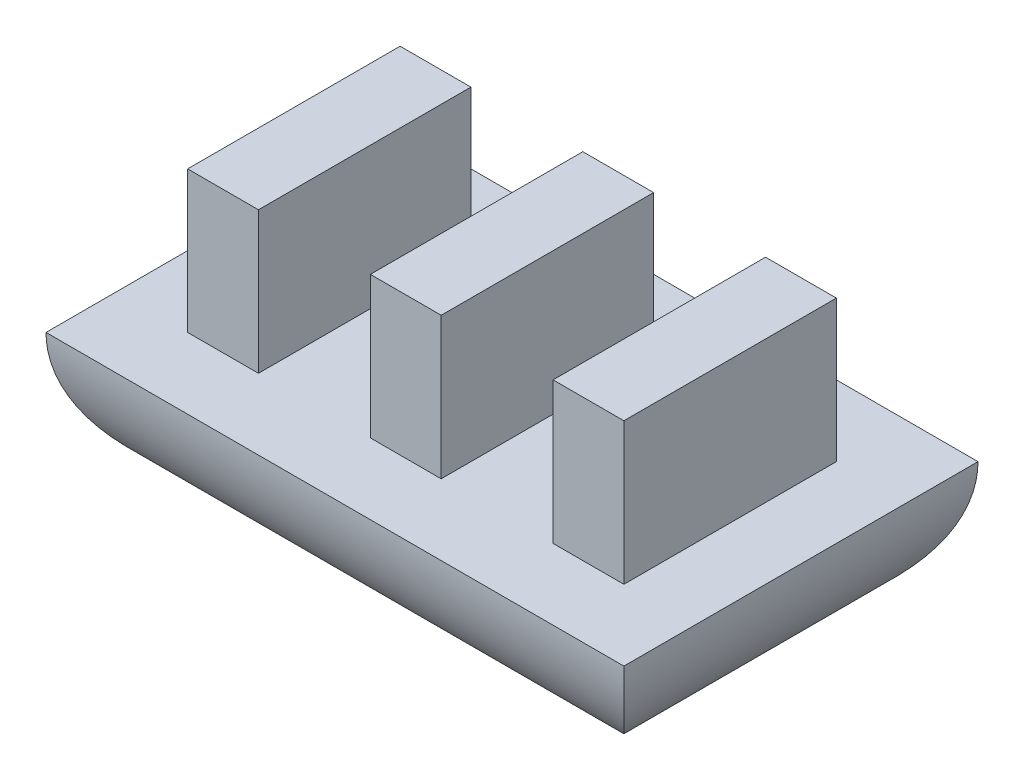
SolidWorks part; units mm, degrees
material "Silicon"
ref_plane "Front Plane" through (0, 0, 0) normal (0, 0, 1) x (1, 0, 0)
ref_plane "Top Plane" through (0, 0, 0) normal (0, 1, 0) x (1, 0, 0)
ref_plane "Right Plane" through (0, 0, 0) normal (1, 0, 0) x (0, 0, -1)
sketch "Sketch1" plane through (0, 0, 0) normal (0, 1, 0) x (1, 0, 0)
  line L0 (0, 3.9688) -> (12.954, 3.9688) construction
  line L1 (0, 0) -> (12.954, 0)
  line L2 (0, 0) -> (0, 7.9375)
  line L3 (0, 7.9375) -> (12.954, 7.9375)
  line L4 (12.954, 0) -> (12.954, 7.9375)
  line L6 (1.5875, 1.5875) -> (3.175, 1.5875)
  line L7 (1.5875, 1.5875) -> (1.5875, 6.35)
  line L8 (1.5875, 6.35) -> (3.175, 6.35)
  line L9 (3.175, 1.5875) -> (3.175, 6.35)
  line L10 (1.5875, 1.5875) -> (3.175, 6.35) construction
  line L11 (1.5875, 6.35) -> (3.175, 1.5875) construction
  line L12 (5.6833, 1.5875) -> (7.2707, 1.5875)
  line L13 (5.6833, 1.5875) -> (5.6833, 6.35)
  line L14 (5.6833, 6.35) -> (7.2707, 6.35)
  line L15 (7.2707, 1.5875) -> (7.2707, 6.35)
  line L16 (5.6833, 1.5875) -> (7.2707, 6.35) construction
  line L17 (5.6833, 6.35) -> (7.2707, 1.5875) construction
  line L18 (9.779, 1.5875) -> (11.3665, 1.5875)
  line L19 (9.779, 1.5875) -> (9.779, 6.35)
  line L20 (9.779, 6.35) -> (11.3665, 6.35)
  line L21 (11.3665, 1.5875) -> (11.3665, 6.35)
  line L22 (9.779, 1.5875) -> (11.3665, 6.35) construction
  line L23 (9.779, 6.35) -> (11.3665, 1.5875) construction
  point P7 (2.3813, 3.9688)
  point P12 (6.477, 3.9688)
  point P17 (10.5727, 3.9688)
  dimension "D1" = 1.5875
  dimension "D2" = 1.5875
  dimension "D3" = 12.954
  dimension "D4" = 1.5875
  dimension "D5" = 7.9375
  dimension "D6" = 4.7625
extrude "Boss-Extrude1" add sketch "Sketch1" against normal blind 3.175 contours L1 L4 L3 L2 L21 L18 L19 L20 L15 L12 L13 L14 L9 L6 L7 L8 | L6 L9 L8 L7 | L12 L15 L14 L13 | L18 L21 L20 L19 region at (0.1519, 0, -3.9688) region at (2.3812, 0, -3.9687) region at (6.477, 0, -3.9687) region at (10.5727, 0, -3.9687)
extrude "Boss-Extrude2" add sketch "Sketch1<3>" along normal blind 3.175 contours L6 L9 L8 L7 | L12 L15 L14 L13 | L18 L21 L20 L19 region at (2.3812, 0, -3.9687) region at (6.477, 0, -3.9687) region at (10.5727, 0, -3.9687)
sketch "Sketch1<3>" plane through (0, 0, 0) normal (0, 1, 0) x (1, 0, 0) same geometry as "Sketch1"
fillet "Fillet1" radius 3.175 4 edges at (12.954, -3.175, -3.9687) (6.477, -3.175, -7.9375) (0, -3.175, -3.9688) (6.477, -3.175, 0)
